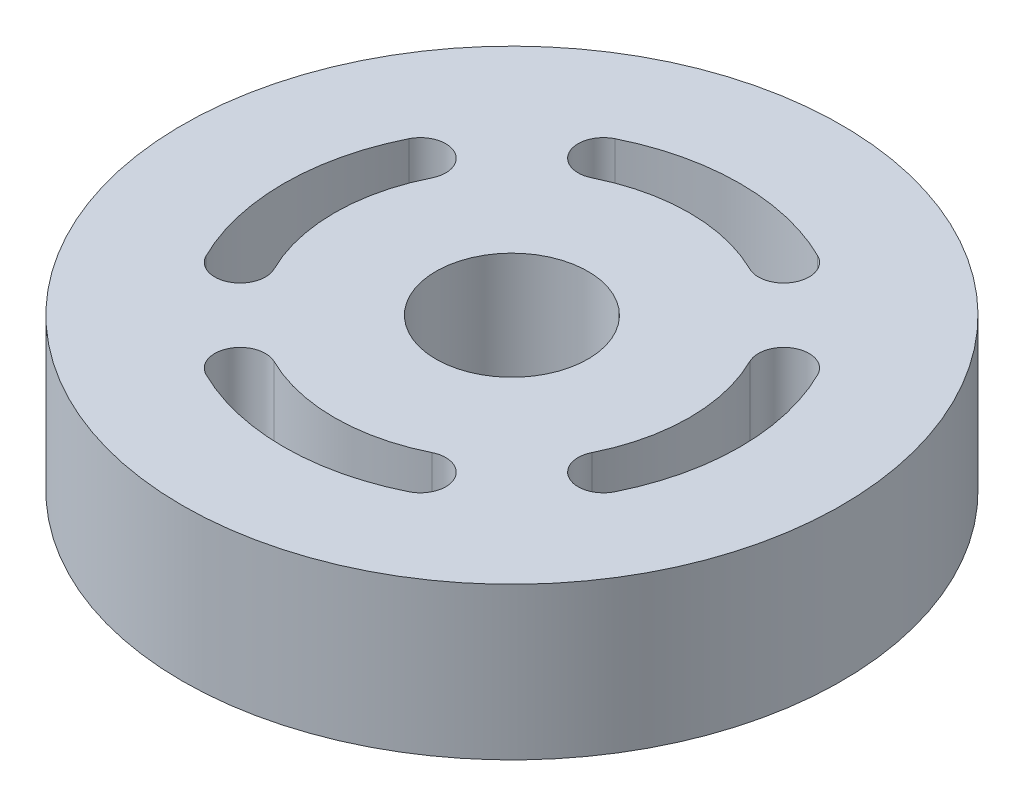
SolidWorks part; units mm, degrees
ref_plane "Front Plane" through (0, 0, 0) normal (0, 0, 1) x (1, 0, 0)
ref_plane "Top Plane" through (0, 0, 0) normal (0, 1, 0) x (1, 0, 0)
ref_plane "Right Plane" through (0, 0, 0) normal (1, 0, 0) x (0, 0, -1)
sketch "Sketch1" plane through (0, 0, 0) normal (0, 1, 0) x (1, 0, 0)
  line L0 (0, 0) -> (0, 14.568) construction
  circle A0 centre (0, 0) radius 13
  circle A1 centre (0, 0) radius 3
  arc A2 (-3.1111, 6.2706) -> (0, 7) centre (0, 0) cw
  arc A3 (-4, 8.0623) -> (0, 9) centre (0, 0) cw
  arc A4 (-3.1111, 6.2706) -> (-4, 8.0623) centre (-3.5556, 7.1665) cw
  arc A5 (3.1111, 6.2706) -> (0, 7) centre (0, 0) ccw
  arc A6 (3.1111, 6.2706) -> (4, 8.0623) centre (3.5556, 7.1665) ccw
  arc A7 (4, 8.0623) -> (0, 9) centre (0, 0) ccw
  point P8 (-3.1999, 7.284)
  dimension "D1" = 6
  dimension "D2" = 26
  dimension "D3" = 7
  dimension "D5" = 8
  dimension "D4" = 2
extrude "Boss-Extrude1" add sketch "Sketch1" along normal blind 6
pattern_circular "CirPattern1" count 4 over 360 about axis through (0, 6, 0) along (0, 1, 0) of face at (0, 3, -8.5311) of face at (0, 3, -6.6353) of face at (4.0035, 3, -6.9442) of face at (-4.0035, 3, -6.9442)
